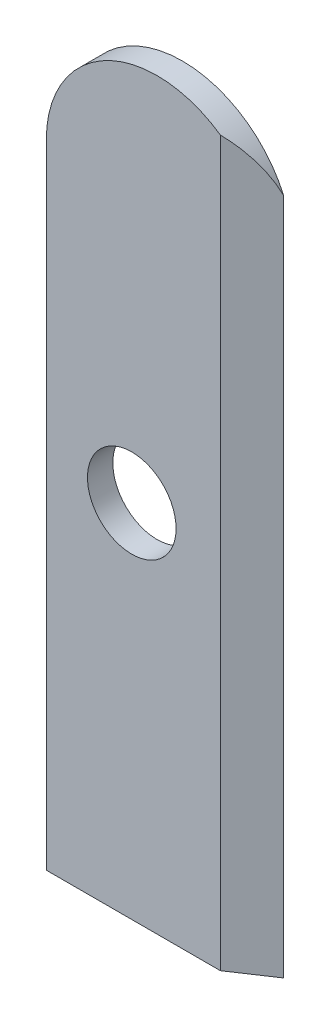
SolidWorks part; units mm, degrees
material "Plain Carbon Steel"
ref_plane "Front Plane" through (0, 0, 0) normal (0, 0, 1) x (1, 0, 0)
ref_plane "Top Plane" through (0, 0, 0) normal (0, 1, 0) x (1, 0, 0)
ref_plane "Right Plane" through (0, 0, 0) normal (1, 0, 0) x (0, 0, -1)
sketch "Sketch2" plane through (0, 0, 0) normal (0, 0, 1) x (1, 0, 0)
  line L0 (0, 0) -> (-7, 0)
  line L1 (-7, 0) -> (-7, 20)
  line L2 (0, 20) -> (0, 0)
  line L3 (-0.3, 0) -> (-0.3, 21.4177)
  line L4 (-0.3, 0) -> (-0.3, 20) construction
  arc A0 (-7, 20) -> (0, 20) centre (-3.5, 20) cw
  point P6 (0, 0)
  point P7 (-3.5, 23.5)
  point P10 (-0.3, 21.4177)
  dimension "D1" = 23.5
  dimension "D2" = 7
  dimension "D3" = 6.7
extrude "Boss-Extrude1" add sketch "Sketch2" along normal blind 0.8 contours A0 L1 L0 L3 region at (-3.6376, 11.4252, 0)
chamfer "Chamfer1" distance 0.8 distance2 1.2 1 edges at (-0.3, 10.7089, 0.8) first distance on face at (-0.3, 10.7089, 0.4)
sketch "Sketch5" plane through (0, 0, 0.8) normal (0, 0, 1) x (1, 0, 0)
  circle A0 centre (-4.3, 11.4) radius 1.4
  point P2 (0, 0)
  point P4 (0, 0)
  dimension "D1" = 2.8
  dimension "D2" = 2.7
  dimension "D3" = 11.4
extrude "Cut-Extrude1" cut sketch "Sketch5" against normal up to next
